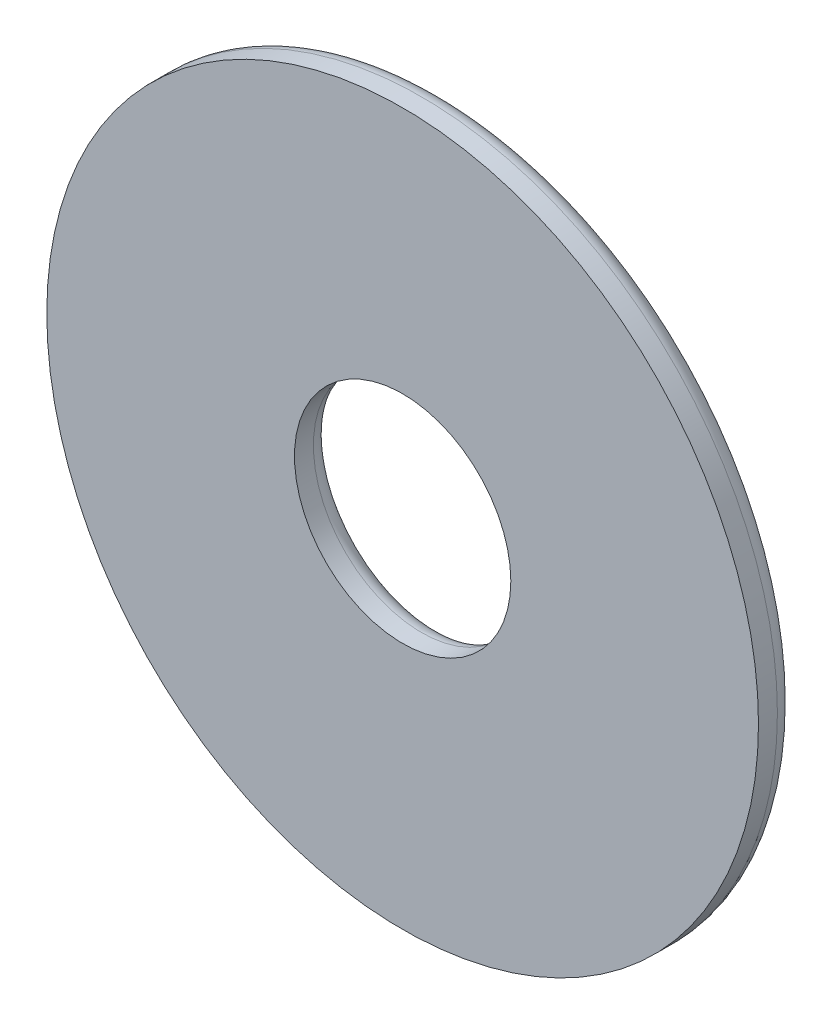
SolidWorks part; units mm, degrees
ref_plane "Front Plane" through (0, 0, 0) normal (0, 0, 1) x (1, 0, 0)
ref_plane "Top Plane" through (0, 0, 0) normal (0, 1, 0) x (1, 0, 0)
ref_plane "Right Plane" through (0, 0, 0) normal (1, 0, 0) x (0, 0, -1)
sketch "Sketch1" plane through (0, 0, 0) normal (0, 0, 1) x (1, 0, 0)
  line L0 (-11.1125, 0) -> (11.1125, 0) construction
  line L1 (0, 11.1125) -> (0, -11.1125) construction
  circle A0 centre (0, 0) radius 11.1125 construction
  circle A1 centre (0, 0) radius 3.3782 construction
  point P4 (0, 0)
  point P8 (0, -3.3782)
  point P9 (3.3782, 0)
  point P10 (0, 3.3782)
  point P11 (-3.3782, 0)
  dimension "OD" = 22.225
  dimension "ID" = 6.7564
sketch "Sketch2" plane through (0, 0, 0) normal (1, 0, 0) x (0, 0, -1)
  line L0 (0.5905, 0) -> (-0.5905, 0) construction
  line L1 (0.5906, 11.1125) -> (-0.5905, 11.1125) construction
  line L2 (0.5906, 11.1125) -> (0.5906, -11.1125) construction
  line L3 (0.5906, -11.1125) -> (-0.5906, -11.1125) construction
  line L4 (-0.5905, 11.1125) -> (-0.5906, -11.1125) construction
  line L5 (-0.5905, 3.3782) -> (0.5905, 3.3782) construction
  line L6 (-0.5905, -3.3782) -> (0.5905, -3.3782) construction
  line L7 (-0.6477, 0) -> (0.6477, 0) construction
  line L8 (0, 11.1125) -> (0, -11.1125) construction
  point P6 (0, 0)
  point P17 (0, 0)
  point P18 (-0.5334, 0)
  point P21 (0.5334, 0)
  dimension "Max Thickness Range" = 1.2954
  dimension "Min Thickness Range" = 1.0668
  dimension "Thickness Range" = 1.1811
sketch "Sketch3" plane through (0, 0, 0) normal (0, 0, 1) x (1, 0, 0)
  line L0 (-11.1125, 0) -> (11.1125, 0) construction
  circle A0 centre (0, 0) radius 11.1125
  circle A1 centre (0, 0) radius 3.3782
  circle A2 centre (0, 0) radius 11.1125 construction
  circle A3 centre (0, 0) radius 3.3782 construction
extrude "Boss-Extrude1" add sketch "Sketch3" along normal up to vertex (0.5906 mm away) and the other way up to vertex (0.5906 mm away) up to point (0, 0, 0.5905) other way up to point (0, 0, -0.5905)
fillet "Fillet1" radius 0.5906 2 edges at (11.1125, 0, -0.5905) (3.3782, 0, -0.5905)
equation "\"D1@Fillet1\" = \"Thickness Range@Sketch2\" * .5"
